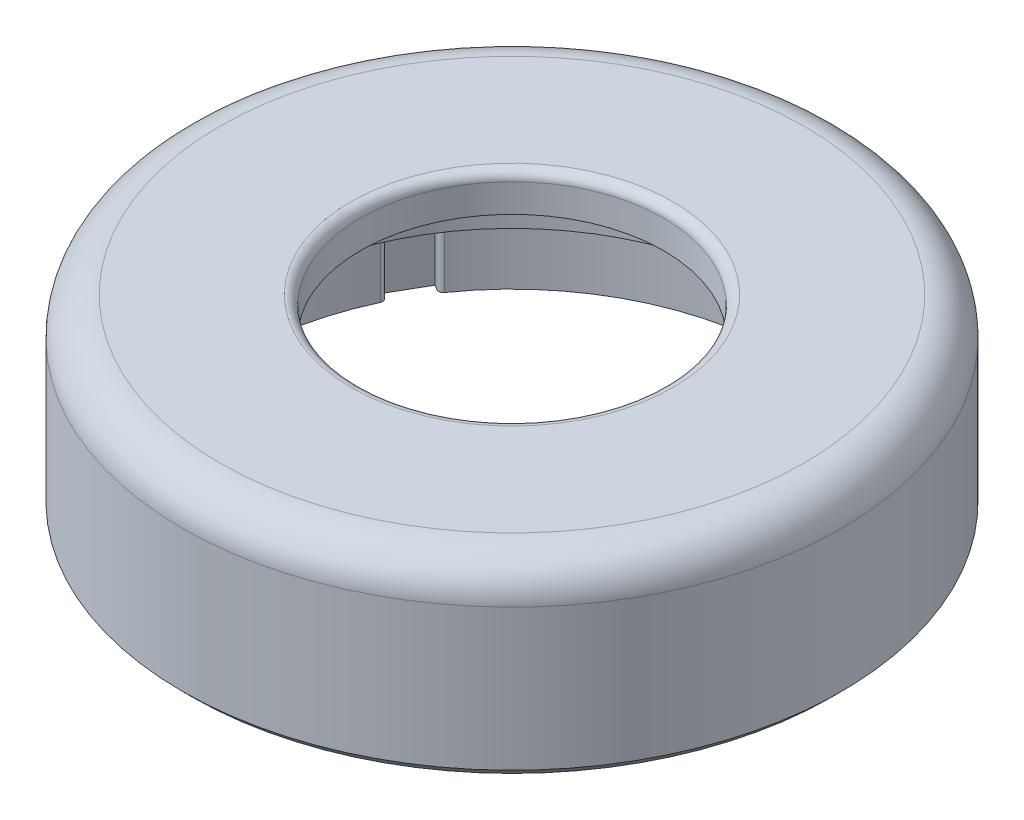
SolidWorks part; units mm, degrees
ref_plane "Front Plane" through (0, 0, 0) normal (0, 0, 1) x (1, 0, 0)
ref_plane "Top Plane" through (0, 0, 0) normal (0, 1, 0) x (1, 0, 0)
ref_plane "Right Plane" through (0, 0, 0) normal (1, 0, 0) x (0, 0, -1)
sketch "Sketch1" plane through (0, 0, 0) normal (0, 1, 0) x (1, 0, 0)
  line L13 (-1.8621, 34.9357) -> (1.0379, 34.9357)
  line L15 (-1.8621, 34.9357) -> (-1.8621, 26.9357)
  line L16 (1.0379, 34.9357) -> (1.0379, 26.98)
  line L17 (1.0379, 26.98) -> (1.0379, 26.28)
  line L18 (1.0379, 26.28) -> (-1.8621, 26.28)
  line L19 (-1.8621, 26.28) -> (-1.8621, 26.9357)
  line L20 (29.7363, -18.3667) -> (22.8464, -14.3889)
  line L21 (22.2402, -14.0389) -> (23.6902, -11.5274)
  line L22 (23.6902, -11.5274) -> (24.258, -11.8553)
  line L23 (31.1863, -15.8553) -> (24.258, -11.8553)
  line L24 (31.1863, -15.8553) -> (29.7363, -18.3667)
  line L25 (-30.7742, -16.569) -> (-23.8844, -12.5911)
  line L26 (-23.2782, -12.2411) -> (-21.8282, -14.7526)
  line L27 (-21.8282, -14.7526) -> (-22.396, -15.0805)
  line L28 (-29.3242, -19.0805) -> (-22.396, -15.0805)
  line L29 (-29.3242, -19.0805) -> (-30.7742, -16.569)
  line L30 (-23.2782, -12.2411) -> (-23.8844, -12.5911)
  line L32 (22.2402, -14.0389) -> (22.8464, -14.3889)
  line L35 (31.1863, -15.8553) -> (29.7363, -18.3667)
  line L36 (31.1863, -15.8553) -> (24.258, -11.8553)
  line L37 (29.7363, -18.3667) -> (22.8464, -14.3889)
  line L38 (22.8464, -14.3889) -> (22.2402, -14.0389)
  line L39 (22.2402, -14.0389) -> (23.6902, -11.5274)
  line L40 (23.6902, -11.5274) -> (24.258, -11.8553)
  line L41 (-29.3242, -19.0805) -> (-30.7742, -16.569)
  line L42 (-29.3242, -19.0805) -> (-22.396, -15.0805)
  line L43 (-30.7742, -16.569) -> (-23.8844, -12.5911)
  line L44 (-23.8844, -12.5911) -> (-23.2782, -12.2411)
  line L45 (-23.2782, -12.2411) -> (-21.8282, -14.7526)
  line L46 (-21.8282, -14.7526) -> (-22.396, -15.0805)
  line L47 (-19.7646, 13.7667) -> (-21.8046, 10.2333)
  line L48 (-2.04, -24) -> (2.04, -24)
  line L49 (-2.04, -24) -> (-2.04, -30)
  line L50 (-2.04, -30) -> (2.04, -30)
  line L51 (2.04, -24) -> (2.04, -30)
  line L52 (-2.04, -24) -> (2.04, -30) construction
  line L53 (-2.04, -30) -> (2.04, -24) construction
  line L54 (-19.7646, 13.7667) -> (-24.9608, 16.7667)
  line L55 (-21.8046, 10.2333) -> (-27.0008, 13.2333)
  line L56 (-24.9608, 16.7667) -> (-27.0008, 13.2333)
  line L57 (21.8046, 10.2333) -> (19.7646, 13.7667)
  line L58 (21.8046, 10.2333) -> (27.0008, 13.2333)
  line L59 (19.7646, 13.7667) -> (24.9608, 16.7667)
  line L60 (27.0008, 13.2333) -> (24.9608, 16.7667)
  circle A0 centre (0, 0) radius 27
  circle A1 centre (0, 0) radius 29
  point P3 (0, 27)
  point P7 (0, -27)
  point P18 (0.1049, -0.1564)
  point P26 (0, 0)
  point P27 (0, 0)
  point P28 (23.3827, -13.5)
  point P34 (0, 0)
  point P36 (-23.3827, -13.5)
  point P43 (0, 0)
  point P58 (0, 0)
  dimension "D1" = 54
  dimension "D6" = 58
  dimension "D2" = 0.7
  dimension "D3" = 3
  dimension "D4" = 2.9
  dimension "D5" = 8
  dimension "D7" = 3
  dimension "D8" = 6
  dimension "D9" = 4.08
  dimension "D10" = 3
sketch "Sketch6" plane through (0, 0, 0) normal (0, 1, 0) x (1, 0, 0)
  line L0 (-18.1, -16.1) -> (-12.1, -22.1)
  line L1 (-18.1, -22.1) -> (18.1, -22.1)
  line L2 (-18.1, -22.1) -> (-18.1, 22.1)
  line L3 (-18.1, 22.1) -> (18.1, 22.1)
  line L4 (18.1, -22.1) -> (18.1, 22.1)
  line L5 (-18.1, -22.1) -> (18.1, 22.1) construction
  line L6 (-18.1, 22.1) -> (18.1, -22.1) construction
  line L7 (-12.1, 22.1) -> (-18.1, 16.1)
  line L8 (18.1, -16.1) -> (12.1, -22.1)
  line L9 (11.9, 22.1) -> (18.1, 16.1)
  circle A0 centre (15.1, -15.8) radius 2
  circle A1 centre (-14.9, -15.8) radius 2
  circle A2 centre (-14.9, 14.4) radius 2
  circle A3 centre (15.1, 14.4) radius 2
  circle A4 centre (0, 0) radius 16.1
  circle A5 centre (-14.9, 14.4) radius 4.5
  circle A6 centre (15.1, 14.4) radius 4.5
  circle A7 centre (-14.9, -15.8) radius 4.5
  circle A8 centre (15.1, -15.8) radius 4.5
  point P0 (0, 0)
  dimension "D8" = 6.3
  dimension "D14" = 9
  dimension "D1" = 44.2
  dimension "D2" = 36.2
  dimension "D3" = 6
  dimension "D4" = 6
  dimension "D5" = 6
  dimension "D6" = 6
  dimension "D7" = 6
  dimension "D9" = 3
  dimension "D12" = 6
  dimension "D13" = 7.7
  dimension "D10" = 2
  dimension "D11" = 2
sketch "Sketch7" plane through (0, 0, 0) normal (0, 1, 0) x (1, 0, 0)
  circle A0 centre (0, 0) radius 35
  dimension "D1" = 70
extrude "Boss-Extrude6" add sketch "Sketch7" along normal blind 20 contours A0
extrude "Display cutout" cut sketch "Sketch6" along normal through all contours A4
extrude "Cut-Extrude6" cut sketch "Sketch1" along normal blind 7 contours A0 L54 L56 L55 | L54 A0 L55 L47 | L51 A0 L32 L21 L22 L58 L57 L59 L17 L18 L19 L54 L47 L55 L30 L26 L27 L49 L48 | A0 L58 L60 L59 | L58 A0 L59 L57 | L49 A0 L51 L48 | A0 L49 L50 L51 | L32 A0 L22 L21 | L30 A0 L27 L26 | L17 A0 L19 L18 | A1 L54 L56 L55 | A1 L49 L50 L51 | A1 L58 L60 L59
fillet "Fillet2" radius 4 1 edges at (0, 20, 35)
fillet "Fillet3" radius 1 1 edges at (0, 20, 16.1)
sketch "Sketch8" plane through (0, 7, 0) normal (0, -1, 0) x (1, 0, 0)
  circle A0 centre (0, 0) radius 23.25
  circle A1 centre (0, 0) radius 27
  dimension "D1" = 46.5
extrude "Cut-Extrude7" cut sketch "Sketch8" against normal blind 9
chamfer "Chamfer1" distance 1 angle 45 1 edges at (0, 0, 35)
fillet "Fillet4" radius 0.5 6 edges at (-2.04, 3.5, 28.9282) (2.04, 3.5, 28.9282) (26.0725, 3.5, -12.6974) (24.0325, 3.5, -16.2308) (-26.0725, 3.5, -12.6974) (-24.0325, 3.5, -16.2308)
sketch "Sketch9" plane through (0, 16, 0) normal (0, -1, 0) x (1, 0, 0)
  circle A0 centre (0, 0) radius 17.85
extrude "Extrude-Thin1" add sketch "Sketch9" along normal blind 1 thin thin type one direction wall 2
fillet "Fillet5" radius 1 1 edges at (0, 15, -17.85)
